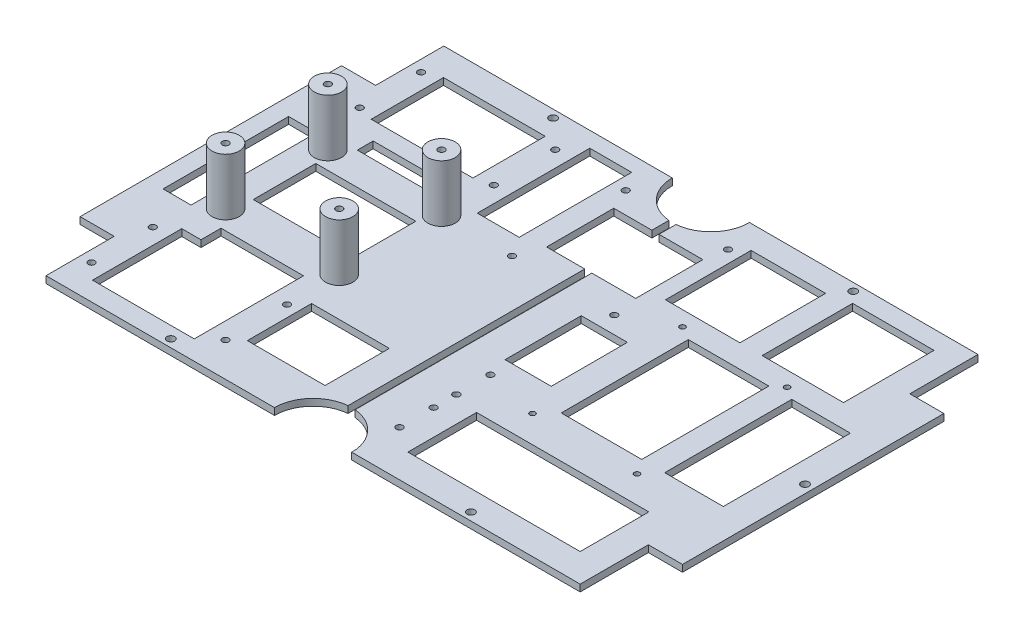
SolidWorks part; units mm, degrees
ref_plane "Płaszczyzna przednia" through (0, 0, 0) normal (0, 0, 1) x (1, 0, 0)
ref_plane "Płaszczyzna górna" through (0, 0, 0) normal (0, 1, 0) x (1, 0, 0)
ref_plane "Płaszczyzna prawa" through (0, 0, 0) normal (1, 0, 0) x (0, 0, -1)
sketch "Sketch1" plane through (0, 0, 0) normal (0, 1, 0) x (1, 0, 0)
  line L16 (-132.5, 87.5) -> (132.5, 87.5)
  line L18 (-132.5, 87.5) -> (-132.5, -87.5)
  line L19 (-132.5, -87.5) -> (132.5, -87.5)
  line L20 (132.5, 87.5) -> (132.5, -87.5)
  line L21 (-132.5, 87.5) -> (132.5, -87.5) construction
  line L22 (-132.5, -87.5) -> (132.5, 87.5) construction
  point P0 (0, 0)
  dimension "D2" = 175
  dimension "D1" = 265
extrude "Boss-Extrude3" add sketch "Sketch1" along normal blind 3
sketch "Sketch2" plane through (0, 3, 0) normal (0, 1, 0) x (1, 0, 0)
  line L0 (132.5, 0) -> (65, 0) construction
  line L1 (132.5, -87.5) -> (132.5, 87.5) construction
  line L2 (-53.5, -45.5) -> (-53.5, 45.5) construction
  line L3 (42, -33) -> (88, -33) construction
  line L4 (42, -33) -> (42, 33) construction
  line L5 (42, 33) -> (88, 33) construction
  line L6 (88, -33) -> (88, 33) construction
  line L7 (42, -33) -> (88, 33) construction
  line L8 (42, 33) -> (88, -33) construction
  line L10 (-132.5, -87.5) -> (-112.5, -87.5) construction
  line L11 (-132.5, -87.5) -> (-132.5, -72.5) construction
  line L12 (-132.5, -72.5) -> (-112.5, -72.5) construction
  line L13 (-112.5, -87.5) -> (-112.5, -72.5) construction
  line L14 (-112.5, -72.5) -> (-53.5, -72.5) construction
  line L15 (-112.5, -72.5) -> (-112.5, -45.5) construction
  line L16 (-112.5, -45.5) -> (-53.5, -45.5) construction
  line L17 (-53.5, -72.5) -> (-53.5, -45.5) construction
  line L18 (-53.5, 45.5) -> (-112.5, 45.5) construction
  line L19 (-53.5, 45.5) -> (-53.5, 72.5) construction
  line L20 (-53.5, 72.5) -> (-112.5, 72.5) construction
  line L21 (-112.5, 45.5) -> (-112.5, 72.5) construction
  line L22 (-53.5, -22.5) -> (-103.5, -22.5) construction
  line L23 (0, 87.5) -> (0, 72.5) construction
  line L28 (132.5, 87.5) -> (-132.5, 87.5) construction
  line L29 (0, 72.5) -> (22.5, 72.5) construction
  line L30 (22.5, 72.5) -> (22.5, 22.5) construction
  line L31 (22.5, 22.5) -> (-22.5, 22.5) construction
  line L32 (-22.5, 22.5) -> (-22.5, 72.5) construction
  line L33 (-22.5, 72.5) -> (0, 72.5) construction
  line L34 (0, -87.5) -> (0, -67.5) construction
  line L35 (-132.5, -87.5) -> (132.5, -87.5) construction
  line L36 (0, -67.5) -> (18, -67.5) construction
  line L37 (18, -67.5) -> (18, -52.5) construction
  line L38 (18, -52.5) -> (18, -42.5) construction
  line L39 (18, -42.5) -> (18, -27.5) construction
  line L40 (-53.5, -22.5) -> (-53.5, 22.5) construction
  line L45 (-53.5, 22.5) -> (-103.5, 22.5) construction
  line L46 (-103.5, -22.5) -> (-103.5, 22.5) construction
  circle A0 centre (88, 33) radius 1.2
  circle A1 centre (42, 33) radius 1.2
  circle A2 centre (88, -33) radius 1.2
  circle A3 centre (42, -33) radius 1.2
  circle A4 centre (18, -67.5) radius 1.45
  circle A5 centre (18, -52.5) radius 1.45
  circle A6 centre (18, -42.5) radius 1.45
  circle A7 centre (18, -27.5) radius 1.45
  circle A8 centre (-53.5, -72.5) radius 1.45
  circle A9 centre (-53.5, -45.5) radius 1.45
  circle A10 centre (-112.5, -45.5) radius 1.45
  circle A11 centre (-112.5, -72.5) radius 1.45
  circle A12 centre (-112.5, 45.5) radius 1.45
  circle A13 centre (-53.5, 45.5) radius 1.45
  circle A14 centre (-53.5, 72.5) radius 1.45
  circle A15 centre (-112.5, 72.5) radius 1.45
  circle A20 centre (-22.5, 22.5) radius 1.45
  circle A21 centre (22.5, 22.5) radius 1.45
  circle A22 centre (-22.5, 72.5) radius 1.45
  circle A23 centre (22.5, 72.5) radius 1.45
  dimension "D3" = 20
  dimension "D11" = 45
  dimension "D1" = 66
  dimension "D2" = 46
  dimension "D4" = 15
  dimension "D5" = 27
  dimension "D6" = 59
  dimension "D7" = 27
  dimension "D8" = 59
  dimension "D9" = 15
  dimension "D10" = 50
  dimension "D12" = 23
  dimension "D13" = 23
extrude "Cut-Extrude1" cut sketch "Sketch2" against normal blind 10
sketch "Sketch3" plane through (0, 3, 0) normal (0, 1, 0) x (1, 0, 0)
  line L0 (132.5, 0) -> (128.9, 0) construction
  line L1 (132.5, -87.5) -> (132.5, 87.5) construction
  line L2 (-132.5, 0) -> (-128.9, 0) construction
  line L3 (-132.5, 87.5) -> (-132.5, -87.5) construction
  line L4 (-128.9, 0) -> (-66, 0) construction
  line L5 (-66, 0) -> (-66, 84.1) construction
  line L6 (-66, 0) -> (-66, -84.1) construction
  line L7 (-66, 84.1) -> (66, 84.1) construction
  line L8 (-66, -84.1) -> (66, -84.1) construction
  circle A0 centre (-66, 84.1) radius 1.7
  circle A1 centre (-128.9, 0) radius 1.7
  circle A2 centre (-66, -84.1) radius 1.7
  circle A3 centre (66, -84.1) radius 1.7
  circle A4 centre (66, 84.1) radius 1.7
  circle A5 centre (128.9, 0) radius 1.7
extrude "Cut-Extrude2" cut sketch "Sketch3" against normal blind 10
sketch "Sketch4" plane through (0, 3, 0) normal (0, 1, 0) x (1, 0, 0)
  line L0 (132.5, 87.5) -> (-132.5, 87.5) construction
  line L1 (-132.5, -87.5) -> (132.5, -87.5) construction
  line L3 (-132.5, 87.5) -> (-117.5, 87.5)
  line L4 (-132.5, 87.5) -> (-132.5, 57.5)
  line L5 (-132.5, 57.5) -> (-117.5, 57.5)
  line L6 (-117.5, 87.5) -> (-117.5, 57.5)
  line L7 (-132.5, -87.5) -> (-117.5, -87.5)
  line L8 (-132.5, -87.5) -> (-132.5, -57.5)
  line L9 (-132.5, -57.5) -> (-117.5, -57.5)
  line L10 (-117.5, -87.5) -> (-117.5, -57.5)
  line L11 (132.5, -87.5) -> (117.5, -87.5)
  line L12 (132.5, -87.5) -> (132.5, -57.5)
  line L13 (132.5, -57.5) -> (117.5, -57.5)
  line L14 (117.5, -87.5) -> (117.5, -57.5)
  line L15 (132.5, 87.5) -> (117.5, 87.5)
  line L16 (132.5, 87.5) -> (132.5, 57.5)
  line L17 (132.5, 57.5) -> (117.5, 57.5)
  line L18 (117.5, 87.5) -> (117.5, 57.5)
  circle A0 centre (0, 87.5) radius 17
  circle A1 centre (0, -87.5) radius 17
  dimension "D1" = 30
  dimension "D2" = 15
  dimension "D3" = 30
  dimension "D4" = 15
extrude "Cut-Extrude3" cut sketch "Sketch4" against normal blind 10
sketch "Sketch5" plane through (0, 3, 0) normal (0, 1, 0) x (1, 0, 0)
  circle A0 centre (-53.5, 22.5) radius 6
  circle A1 centre (-53.5, -22.5) radius 6
  circle A2 centre (-103.5, -22.5) radius 6
  circle A3 centre (-103.5, 22.5) radius 6
  dimension "D1" = 45
  dimension "D2" = 50
  dimension "D3" = 50
  dimension "D4" = 45
extrude "Boss-Extrude4" add sketch "Sketch5" along normal blind 25
sketch "Sketch6" plane through (0, 28, 0) normal (0, 1, 0) x (1, 0, 0)
  circle A0 centre (-103.5, 22.5) radius 1.45
  circle A1 centre (-53.5, 22.5) radius 1.45
  circle A2 centre (-53.5, -22.5) radius 1.45
  circle A3 centre (-103.5, -22.5) radius 1.45
extrude "Cut-Extrude4" cut sketch "Sketch6" against normal blind 16
sketch "Sketch7" plane through (0, 3, 0) normal (0, 1, 0) x (1, 0, 0)
  line L1 (-1.5668, -70.5724) -> (1.5668, -70.5724)
  line L2 (-1.5668, -70.5724) -> (-1.5668, 70.5724)
  line L3 (-1.5668, 70.5724) -> (1.5668, 70.5724)
  line L4 (1.5668, -70.5724) -> (1.5668, 70.5724)
  line L5 (-1.5668, -70.5724) -> (1.5668, 70.5724) construction
  line L6 (-1.5668, 70.5724) -> (1.5668, -70.5724) construction
  arc A0 (-17, 87.5) -> (17, 87.5) centre (0, 87.5) ccw construction
  point P0 (0, 0)
extrude "Cut-Extrude5" cut sketch "Sketch7" against normal blind 16
sketch "Sketch8" plane through (0, 3, 0) normal (0, 1, 0) x (1, 0, 0)
  line L1 (-100.9203, -12.8956) -> (-56.9163, -12.8956)
  line L2 (-100.9203, -12.8956) -> (-100.9203, 14.6069)
  line L3 (-100.9203, 14.6069) -> (-56.9163, 14.6069)
  line L4 (-56.9163, -12.8956) -> (-56.9163, 14.6069)
  line L5 (-112.5004, -28.6939) -> (-124.8041, -28.6939)
  line L6 (-112.5004, -28.6939) -> (-112.5004, 26.5182)
  line L7 (-112.5004, 26.5182) -> (-124.8041, 26.5182)
  line L8 (-124.8041, -28.6939) -> (-124.8041, 26.5182)
  line L9 (-105.568, 43.6252) -> (-60.8155, 43.6252)
  line L10 (-105.568, 43.6252) -> (-105.568, 75.4196)
  line L11 (-105.568, 75.4196) -> (-60.8155, 75.4196)
  line L12 (-60.8155, 43.6252) -> (-60.8155, 75.4196)
  line L21 (-46.4644, 80.6781) -> (-28.0466, 80.6781)
  line L22 (-46.4644, 80.6781) -> (-46.4644, 31.1977)
  line L23 (-46.4644, 31.1977) -> (-28.0466, 31.1977)
  line L24 (-28.0466, 80.6781) -> (-28.0466, 31.1977)
  line L25 (-96.8686, 28.8192) -> (-61.2463, 28.8192)
  line L26 (-96.8686, 28.8192) -> (-96.8686, 35.7775)
  line L27 (-96.8686, 35.7775) -> (-61.2463, 35.7775)
  line L28 (-61.2463, 28.8192) -> (-61.2463, 35.7775)
  line L29 (-105.568, -78.974) -> (-60.8155, -78.974)
  line L30 (-105.568, -78.974) -> (-105.568, -39.7113)
  line L31 (-105.568, -39.7113) -> (-60.8155, -39.7113)
  line L32 (-60.8155, -78.974) -> (-60.8155, -39.7113)
  line L33 (-60.8155, -39.7113) -> (-97.1012, -39.7113)
  line L34 (-60.8155, -39.7113) -> (-60.8155, -30.8994)
  line L35 (-60.8155, -30.8994) -> (-97.1012, -30.8994)
  line L36 (-97.1012, -39.7113) -> (-97.1012, -30.8994)
  line L37 (-48.4867, -67.9542) -> (-14.283, -67.9542)
  line L38 (-48.4867, -67.9542) -> (-48.4867, -39.6743)
  line L39 (-48.4867, -39.6743) -> (-14.283, -39.6743)
  line L40 (-14.283, -67.9542) -> (-14.283, -39.6743)
  line L42 (-18.3295, 33.5586) -> (20.8655, 33.5586)
  line L43 (-18.3295, 33.5586) -> (-18.3295, 63.0967)
  line L44 (-18.3295, 63.0967) -> (20.8655, 63.0967)
  line L45 (20.8655, 33.5586) -> (20.8655, 63.0967)
  line L46 (27.9519, 39.5751) -> (60.6973, 39.5751)
  line L47 (27.9519, 39.5751) -> (27.9519, 77.2415)
  line L48 (27.9519, 77.2415) -> (60.6973, 77.2415)
  line L49 (60.6973, 39.5751) -> (60.6973, 77.2415)
  line L50 (70.4634, 39.5751) -> (106.2727, 39.5751)
  line L51 (70.4634, 39.5751) -> (70.4634, 79.3709)
  line L52 (70.4634, 79.3709) -> (106.2727, 79.3709)
  line L53 (106.2727, 39.5751) -> (106.2727, 79.3709)
  line L54 (48.1174, -26.46) -> (83.5385, -26.46)
  line L55 (48.1174, -26.46) -> (48.1174, 29.4455)
  line L56 (48.1174, 29.4455) -> (83.5385, 29.4455)
  line L57 (83.5385, -26.46) -> (83.5385, 29.4455)
  line L58 (35.7695, -18.51) -> (15.4663, -18.51)
  line L59 (35.7695, -18.51) -> (35.7695, 14.991)
  line L60 (35.7695, 14.991) -> (15.4663, 14.991)
  line L61 (15.4663, -18.51) -> (15.4663, 14.991)
  line L62 (29.296, -75.102) -> (105.0854, -75.102)
  line L63 (29.296, -75.102) -> (29.296, -44.891)
  line L64 (29.296, -44.891) -> (105.0854, -44.891)
  line L65 (105.0854, -75.102) -> (105.0854, -44.891)
  line L66 (93.643, -26.46) -> (119.4209, -26.46)
  line L67 (93.643, -26.46) -> (93.643, 29.4455)
  line L68 (93.643, 29.4455) -> (119.4209, 29.4455)
  line L69 (119.4209, -26.46) -> (119.4209, 29.4455)
  line M21 (-1.5668, -70.5724) -> (-1.5668, 70.5724)
extrude "Cut-Extrude6" cut sketch "Sketch8" against normal blind 10 contours L9 L12 L11 L10 | L8 L5 L6 L7 | L1 L4 L3 L2 | L29 L32 L31 L30 | L36 L31 L34 L35 | L25 L28 L27 L26 | L24 L21 L22 L23 | L37 L40 L39 L38 | L44 L43 L42 M21 | L42 L45 L44 M21 | L46 L49 L48 L47 | L50 L53 L52 L51 | L54 L57 L56 L55 | L66 L69 L68 L67 | L62 L65 L64 L63 | L61 L58 L59 L60 region at (-78.9183, 3, -0.8557) region at (-118.6522, 3, 1.0878) region at (-83.1917, 3, -59.5224) region at (-37.2555, 3, -55.9379) region at (-79.0574, 3, -32.2983) region at (-83.1917, 3, 59.3427) region at (-78.9584, 3, 35.3054) region at (-31.3848, 3, 53.8142) region at (-9.9482, 3, -48.3276) region at (9.6493, 3, -48.3276) region at (44.3246, 3, -58.4083) region at (88.3681, 3, -59.473) region at (65.8279, 3, -1.4928) region at (25.6179, 3, 1.7595) region at (67.1907, 3, 59.9965) region at (106.5319, 3, -1.4928)
